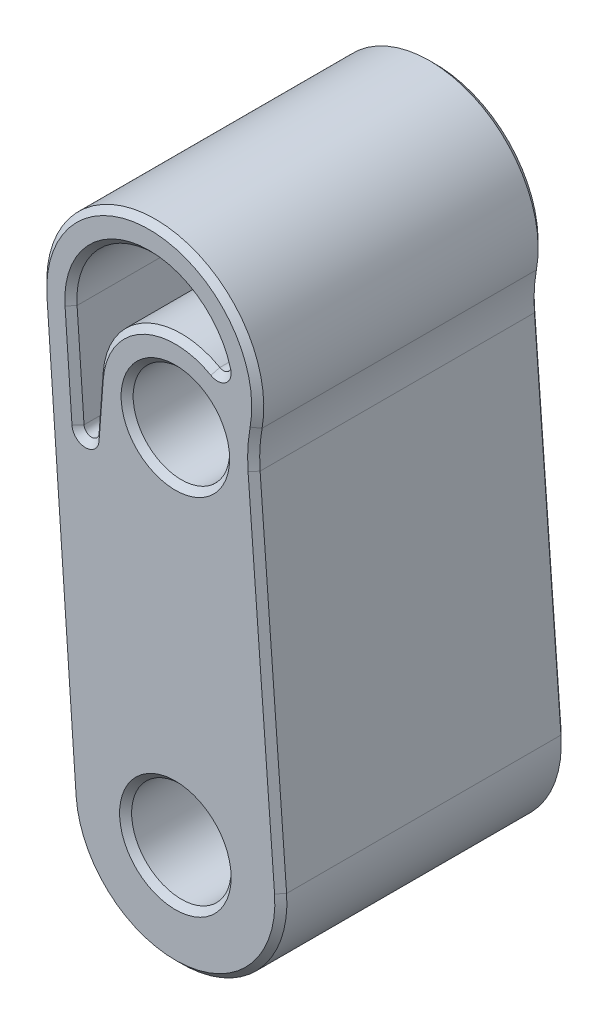
SolidWorks part; units mm, degrees
ref_plane "Front" through (0, 0, 0) normal (0, 0, 1) x (1, 0, 0)
ref_plane "Top" through (0, 0, 0) normal (0, 1, 0) x (1, 0, 0)
ref_plane "Right" through (0, 0, 0) normal (1, 0, 0) x (0, 0, -1)
sketch "Sketch1" plane through (0, 0, 0) normal (0, 0, 1) x (1, 0, 0)
  line L3 (-2.6, 0) -> (-1.6, 0) construction
  line L23 (1.65, -12) -> (2.65, -12) construction
  line L33 (-2.5927, 0.195) -> (-3.4901, -11.7375)
  line L34 (3.4901, -11.7375) -> (2.5927, 0.195)
  circle A0 centre (0, 0) radius 2.6 construction
  circle A3 centre (0, 0) radius 1.6
  circle A12 centre (0, -12) radius 1.65
  circle A13 centre (0, -12) radius 4.25 construction
  arc A22 (-2.5927, 0.195) -> (2.5927, 0.195) centre (0, 0) cw
  arc A28 (-3.4901, -11.7375) -> (3.4901, -11.7375) centre (0, -12) ccw
  dimension "D1" = 3.2
  dimension "D3" = 8.5
  dimension "D6" = 3.3
  dimension "D7" = 3.5
  dimension "D2" = 1
  dimension "D5" = 12
extrude "Boss-Extrude1" add sketch "Sketch1" along normal mid plane 9.5 contours A3 region at (0, -7.006, 0)
sketch "Sketch2" plane through (0, 0, 0) normal (0, 0, 1) x (1, 0, 0)
  line L0 (-3.4915, -12.2435) -> (-4.4576, 1.6074)
  line L1 (0, 0) -> (0, 8.0844) construction
  line L2 (0, 0) -> (-0.8664, 1.8579) construction
  line L3 (-0.8664, 1.8579) -> (-2.2187, 4.7581) construction
  line L4 (-2.2187, 4.7581) -> (-2.3878, 5.1206) construction
  arc A0 (-4.4576, 1.6074) -> (2.5206, 0.6378) centre (-0.8664, 1.8579) cw
  circle A1 centre (0, 0) radius 5.25 construction
  arc A2 (-3.4901, -11.7375) -> (3.4901, -11.7375) centre (0, -12) ccw construction
  arc A4 (2.5927, 0.195) -> (-2.5927, 0.195) centre (0, 0) ccw construction
  dimension "D2" = 10.5
  dimension "D4" = 3.6
  dimension "D1" = 0.4
  dimension "D3" = 25
extrude "Spring" add sketch "Sketch2" along normal through all and the other way through all thin thin type one direction wall 1
fillet "Spring Inside Fillets" radius 0.25 2 edges at (-2.9891, -5.0754, 0) (1.7324, 1.9388, 0)
fillet "Spring Outside Fillets" radius 5 1 edges at (2.5206, 0.6378, 0)
chamfer "Deburs" distance 0.2 angle 45 26 edges at (1.6, 0, -4.75) (1.65, -12, -4.75) (-1.3048, 4.4207, -4.75) (1.5529, 2.2861, -4.75) (-2.9804, -1.8672, -4.75) (-3.3446, 0.0212, -4.75) (0.253, -15.4908, -4.75) (3.0505, -5.8916, -4.75) (-1.2267, 2.2924, -4.75) (2.6034, 0.5883, -4.75) (-0.6702, 5.4526, -4.75) (-3.9746, -5.3181, -4.75) (1.65, -12, 4.75) (1.6, 0, 4.75) (1.5529, 2.2861, 4.75) (-1.3048, 4.4207, 4.75) (-3.3446, 0.0212, 4.75) (-2.9804, -1.8672, 4.75) (-0.6702, 5.4526, 4.75) (2.6034, 0.5883, 4.75) (-1.2267, 2.2924, 4.75) (3.0505, -5.8916, 4.75) (0.253, -15.4908, 4.75) (-3.9746, -5.3181, 4.75) (-2.6615, -0.7205, -4.75) (-2.6615, -0.7205, 4.75)
sketch "Sketch3" plane through (-4.3245, -0.3016, 0) normal (-0.9976, -0.0696, 0) x (0, 0, 1)
  line L1 (0, -0.5863) -> (0, -9.4709) construction
  line L6 (4.55, 1.9137) -> (-4.55, 1.9137) construction
  line L8 (4.55, -11.9709) -> (-4.55, -11.9709) construction
  dimension "D1" = 2.5
  dimension "D2" = 2.5
sketch "Sketch4" plane through (-4.3245, -0.3016, 0) normal (-0.9976, -0.0696, 0) x (0, 0, 1)
  line L0 (0, -0.5863) -> (0, -9.4709)
  line L1 (-2, -2.5863) -> (0, -0.5863)
  line L2 (0, -0.5863) -> (2, -2.5863)
  line L3 (0, -0.5863) -> (0, -9.4709) construction
  line L6 (0, -11.9519) -> (0, 0.0141) construction
  dimension "D1" = 45
  dimension "D2" = 2
extrude "Arrow Point" add sketch "Sketch4" along normal blind 0.2 draft 55 thin contours L1 | L2 thin type one direction wall 0.8
sketch "Sketch5" plane through (-4.3245, -0.3016, 0) normal (-0.9976, -0.0696, 0) x (0, 0, 1)
  line L0 (0, -0.9902) -> (0, -9.4709)
  line L1 (0, -0.5863) -> (0, -9.4709) construction
extrude "Arrow Shaft" add sketch "Sketch5" along normal blind 0.2 draft 55 thin thin type mid plane wall 0.8
equation "\"D1@Sketch1\"=\"Clearance Hole Diameter@Box Assy.Assembly\"+.05mm"
equation "\"D6@Sketch1\"=\"Clearance Hole Diameter@Box Assy.Assembly\"+.15mm"
